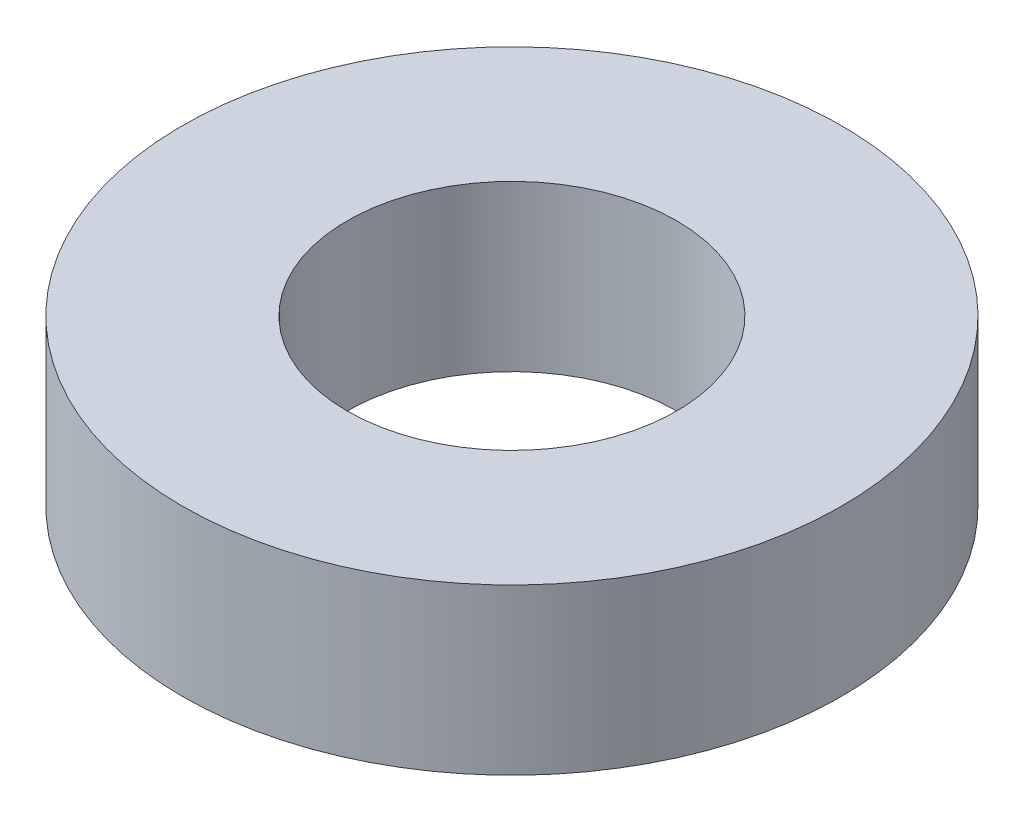
SolidWorks part; units mm, degrees
ref_plane "Front Plane" through (0, 0, 0) normal (0, 0, 1) x (1, 0, 0)
ref_plane "Top Plane" through (0, 0, 0) normal (0, 1, 0) x (1, 0, 0)
ref_plane "Right Plane" through (0, 0, 0) normal (1, 0, 0) x (0, 0, -1)
sketch "Sketch1" plane through (0, 0, 0) normal (0, 1, 0) x (1, 0, 0)
  circle A0 centre (0, 0) radius 50
  dimension "FLANGE_OD" = 100
extrude "Boss-Extrude1" add sketch "Sketch1" along normal blind 25
sketch "Sketch2" plane through (0, 0, 0) normal (0, 1, 0) x (1, 0, 0)
  circle A0 centre (0, 0) radius 25
  dimension "BORE_D" = 50
extrude "Cut-Extrude1" cut sketch "Sketch2" along normal through all
sketch "Sketch3" plane through (0, 25, 0) normal (0, 1, 0) x (1, 0, 0)
  circle A0 centre (0, 0) radius 19.7867 construction
  circle A1 centre (-19.7867, 0) radius 3.9559
  dimension "BOLT_D" = 7.9119
  dimension "BOLT_PCD" = 39.5734
extrude "Cut-Extrude2" cut sketch "Sketch3" against normal blind 21.9423 rebuild error yes
pattern_circular "CirPattern1" count 3 over 360 rebuild error yes
